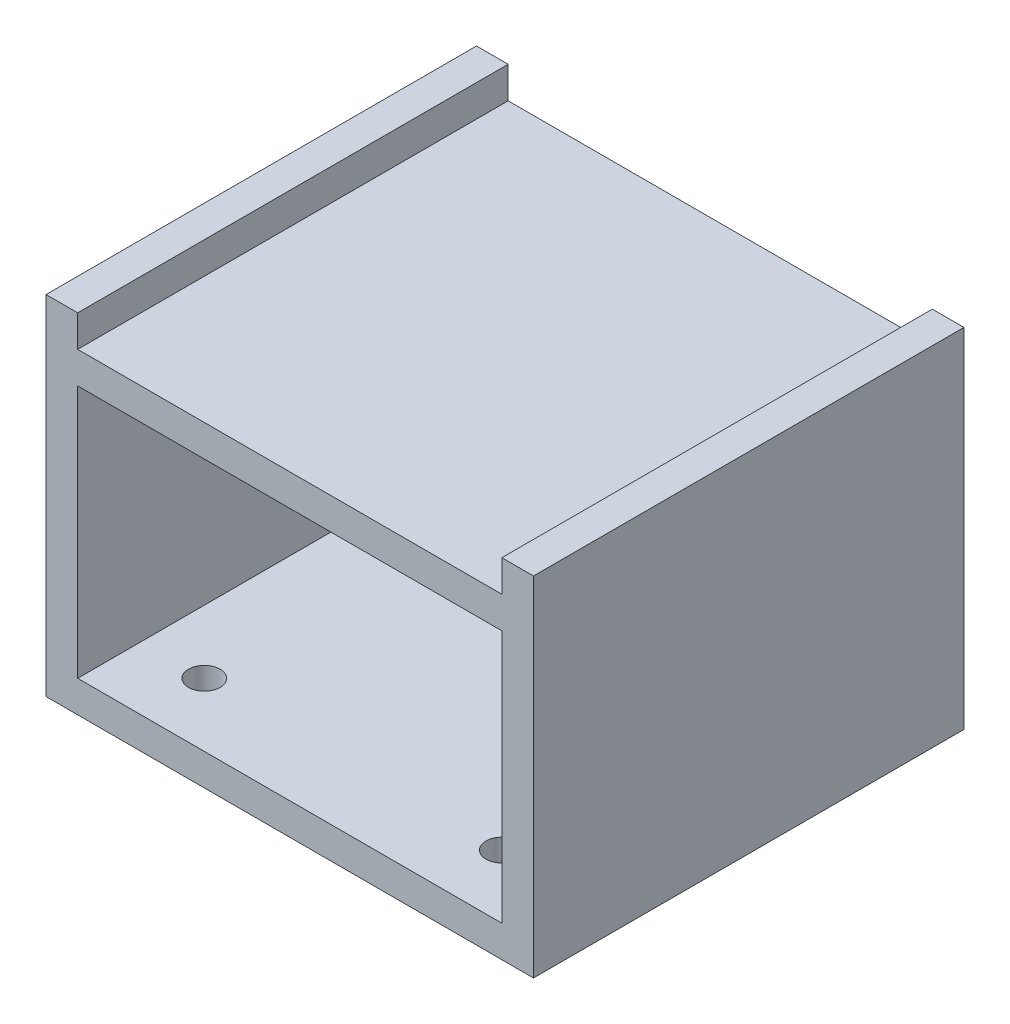
SolidWorks part; units mm, degrees
material "ABS"
ref_plane "Front Plane" through (0, 0, 0) normal (0, 0, 1) x (1, 0, 0)
ref_plane "Top Plane" through (0, 0, 0) normal (0, 1, 0) x (1, 0, 0)
ref_plane "Right Plane" through (0, 0, 0) normal (1, 0, 0) x (0, 0, -1)
sketch "Sketch1" plane through (0, 0, 0) normal (1, 0, 0) x (0, 0, -1)
  line L1 (-43.18, -31.75) -> (43.18, -31.75)
  line L2 (-43.18, -31.75) -> (-43.18, 31.75)
  line L3 (-43.18, 31.75) -> (43.18, 31.75)
  line L4 (43.18, -31.75) -> (43.18, 31.75)
  line L5 (-43.18, -31.75) -> (43.18, 31.75) construction
  line L6 (-43.18, 31.75) -> (43.18, -31.75) construction
  point P0 (0, 0)
  dimension "D1" = 86.36
  dimension "D2" = 63.5
extrude "Boss-Extrude1" add sketch "Sketch1" along normal blind 97.79
sketch "Sketch2" plane through (0, 31.75, 0) normal (0, 1, 0) x (1, 0, 0)
  line L0 (48.895, 43.18) -> (48.895, -43.18) construction
  line L1 (97.79, 43.18) -> (0, 43.18) construction
  line L2 (97.79, -43.18) -> (0, -43.18) construction
  line L3 (97.79, -43.18) -> (91.44, -43.18)
  line L4 (0, 43.18) -> (6.35, 43.18)
  line L5 (0, 43.18) -> (0, -43.18)
  line L6 (0, -43.18) -> (6.35, -43.18)
  line L7 (6.35, 43.18) -> (6.35, -43.18)
  line L8 (97.79, 43.18) -> (97.79, -43.18)
  line L9 (97.79, 43.18) -> (91.44, 43.18)
  line L10 (91.44, 43.18) -> (91.44, -43.18)
  dimension "D1" = 6.35
extrude "Boss-Extrude2" add sketch "Sketch2" along normal blind 6.35
sketch "Sketch4" plane through (0, 0, 0) normal (0, 0, 1) x (1, 0, 0)
  line L0 (6.35, 25.4) -> (6.35, -25.4)
  line L1 (6.35, -25.4) -> (91.44, -25.4)
  line L2 (91.44, -25.4) -> (91.44, 25.4)
  line L3 (91.44, 25.4) -> (91.44, 25.4)
  line L4 (91.44, 25.4) -> (91.44, 25.4)
  line L5 (91.44, 25.4) -> (6.35, 25.4)
  line L6 (6.35, 25.4) -> (6.35, 25.4)
  line L7 (6.35, 25.4) -> (6.35, 25.4)
  line L8 (0, 38.1) -> (0, -31.75)
  line L9 (0, -31.75) -> (97.79, -31.75)
  line L10 (97.79, -31.75) -> (97.79, 38.1)
  line L11 (97.79, 38.1) -> (91.44, 38.1)
  line L12 (91.44, 38.1) -> (91.44, 31.75)
  line L13 (91.44, 31.75) -> (6.35, 31.75)
  line L14 (6.35, 31.75) -> (6.35, 38.1)
  line L15 (6.35, 38.1) -> (0, 38.1)
  line L16 (0, 38.1) -> (0, -31.75) construction
  line L17 (0, -31.75) -> (97.79, -31.75) construction
  line L18 (97.79, -31.75) -> (97.79, 38.1) construction
  line L19 (97.79, 38.1) -> (91.44, 38.1) construction
  line L20 (91.44, 38.1) -> (91.44, 31.75) construction
  line L21 (91.44, 31.75) -> (6.35, 31.75) construction
  line L22 (6.35, 31.75) -> (6.35, 38.1) construction
  line L23 (6.35, 38.1) -> (0, 38.1) construction
  dimension "D1" = 0
  dimension "D2" = 6.35
extrude "Cut-Extrude2" cut sketch "Sketch4" against normal through all both and the other way through all
sketch "Sketch5" plane through (0, -25.4, 0) normal (0, 1, 0) x (1, 0, 0)
  line L0 (48.895, 43.18) -> (48.895, -43.18) construction
  line L1 (91.44, 43.18) -> (6.35, 43.18) construction
  line L2 (91.44, -43.18) -> (6.35, -43.18) construction
  line L3 (0, 0) -> (97.79, 0) construction
  line L4 (97.79, -43.18) -> (97.79, 43.18) construction
  line L6 (0, 43.18) -> (0, -43.18) construction
  circle A0 centre (19.05, 30.48) radius 3.175
  circle A1 centre (78.74, 30.48) radius 3.175
  circle A2 centre (78.74, -30.48) radius 3.175
  circle A3 centre (19.05, -30.48) radius 3.175
  dimension "D1" = 6.35
  dimension "D2" = 12.7
  dimension "D3" = 19.05
extrude "Cut-Extrude3" cut sketch "Sketch5" against normal through all
